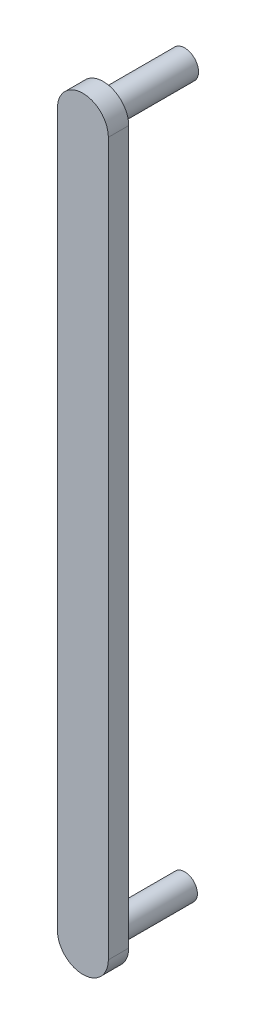
SolidWorks part; units mm, degrees
ref_plane "Front Plane" through (0, 0, 0) normal (0, 0, 1) x (1, 0, 0)
ref_plane "Top Plane" through (0, 0, 0) normal (0, 1, 0) x (1, 0, 0)
ref_plane "Right Plane" through (0, 0, 0) normal (1, 0, 0) x (0, 0, -1)
sketch "Sketch1" plane through (0, 0, 0) normal (0, 0, 1) x (1, 0, 0)
  line L0 (-3.175, 0) -> (-3.175, -88.9)
  line L1 (3.175, 0) -> (3.175, -88.9)
  arc A0 (3.175, 0) -> (-3.175, 0) centre (0, 0) ccw
  arc A1 (3.175, -88.9) -> (-3.175, -88.9) centre (0, -88.9) cw
  circle A2 centre (0, 0) radius 1.5875
  circle A3 centre (0, -88.9) radius 1.5875
  dimension "D3" = 3.175
  dimension "D4" = 3.175
  dimension "D5" = 3.175
  dimension "D1" = 3.175
  dimension "D2" = 88.9
extrude "Boss-Extrude1" add sketch "Sketch1" along normal blind 2.54
sketch "Sketch2" plane through (0, 0, 2.54) normal (0, 0, 1) x (1, 0, 0)
  circle A0 centre (0, 0) radius 1.7298
  circle A1 centre (0, -88.9) radius 1.5875
extrude "Boss-Extrude2" add sketch "Sketch2" against normal blind 12.7
